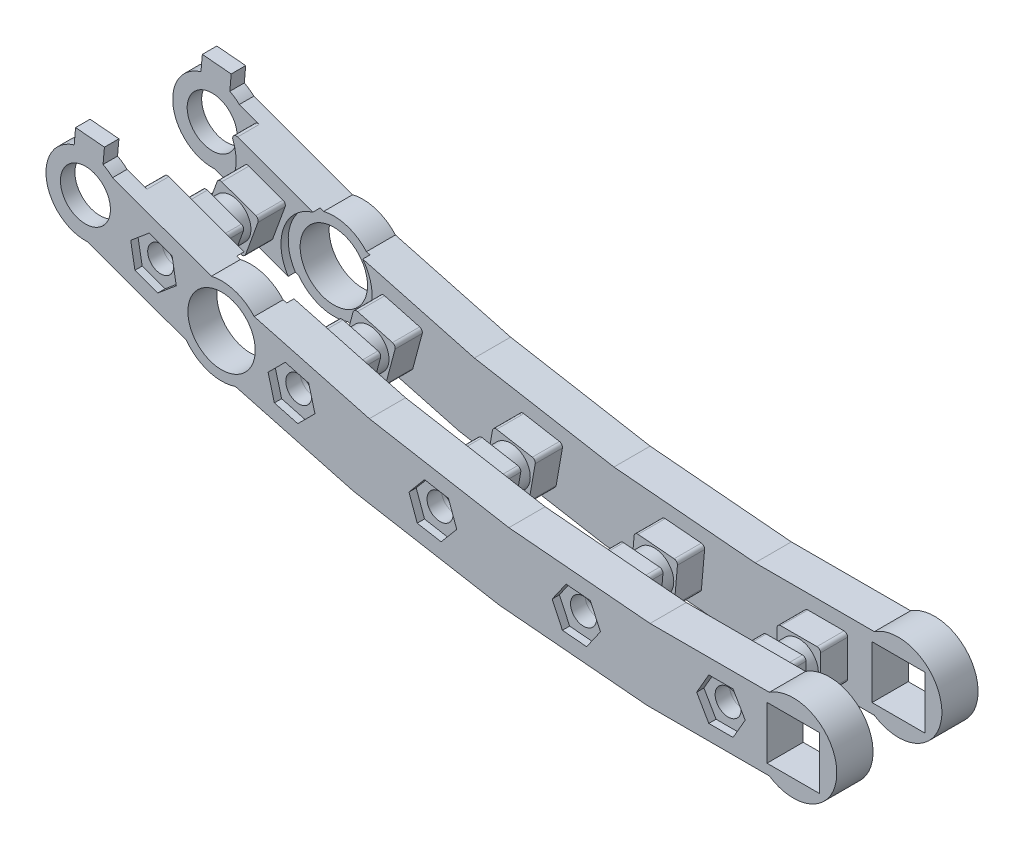
SolidWorks part; units mm, degrees
material "ABS"
ref_plane "正面" through (0, 0, 0) normal (0, 0, 1) x (1, 0, 0)
ref_plane "平面" through (0, 0, 0) normal (0, 1, 0) x (1, 0, 0)
ref_plane "右側面" through (0, 0, 0) normal (1, 0, 0) x (0, 0, -1)
sketch "ｽｹｯﾁ1" plane through (0, 0, 0) normal (0, 0, 1) x (1, 0, 0)
  line L0 (0, 0) -> (-20, 0) construction
  line L1 (3.64, -3.64) -> (-3.64, -3.64)
  line L2 (3.64, -3.64) -> (3.64, 3.64)
  line L3 (3.64, 3.64) -> (-3.64, 3.64)
  line L4 (-3.64, -3.64) -> (-3.64, 3.64)
  line L5 (3.64, -3.64) -> (-3.64, 3.64) construction
  line L6 (3.64, 3.64) -> (-3.64, -3.64) construction
  line L7 (-20, 0) -> (-39.9239, 1.7431) construction
  line L8 (-39.9239, 1.7431) -> (-59.62, 5.2161) construction
  line L9 (-59.62, 5.2161) -> (-78.9386, 10.3925) construction
  line L10 (-78.9386, 10.3925) -> (-97.7324, 17.2329) construction
  line L11 (0, 5) -> (-19.7817, 5) construction
  line L18 (-19.7817, 5) -> (-39.2706, 6.7051) construction
  line L19 (-39.2706, 6.7051) -> (-58.5368, 10.1022) construction
  line L20 (-58.5368, 10.1022) -> (-77.4336, 15.1656) construction
  line L21 (-77.4336, 15.1656) -> (-96.0223, 21.9313) construction
  line L22 (0, -5) -> (-20.2183, -5) construction
  line L23 (-20.2183, -5) -> (-40.5771, -3.2188) construction
  line L24 (-40.5771, -3.2188) -> (-60.7033, 0.3299) construction
  line L25 (-60.7033, 0.3299) -> (-80.4435, 5.6193) construction
  line L26 (-80.4435, 5.6193) -> (-99.4425, 12.5344) construction
  line L27 (-93.9846, 21.1896) -> (-77.4336, 15.1656)
  line L28 (-77.4336, 15.1656) -> (-58.5368, 10.1022)
  line L29 (-58.5368, 10.1022) -> (-39.2706, 6.7051)
  line L30 (-39.2706, 6.7051) -> (-19.7817, 5)
  line L31 (-19.7817, 5) -> (-3.3166, 5)
  line L32 (-3.3166, -5) -> (-20.2183, -5)
  line L33 (-20.2183, -5) -> (-40.5771, -3.2188)
  line L34 (-40.5771, -3.2188) -> (-60.7033, 0.3299)
  line L35 (-60.7033, 0.3299) -> (-80.4435, 5.6193)
  line L36 (-80.4435, 5.6193) -> (-97.4048, 11.7927)
  circle A0 centre (-10, 0) radius 1.8
  circle A1 centre (-29.9619, 0.8716) radius 1.8
  circle A2 centre (-49.772, 3.4796) radius 1.8
  circle A3 centre (-69.2793, 7.8043) radius 1.8
  circle A4 centre (-88.3355, 13.8127) radius 1.8
  circle A5 centre (-97.7324, 17.2329) radius 3.45
  arc A6 (-3.3166, -5) -> (-3.3166, 5) centre (0, 0) ccw
  arc A7 (-93.9846, 21.1896) -> (-97.4048, 11.7927) centre (-97.7324, 17.2329) ccw
  point P0 (0, 0)
  dimension "D8" = 3.6
  dimension "D9" = 6.9
  dimension "D10" = 12
  dimension "D13" = 10.9
  dimension "D1" = 7.28
  dimension "D2" = 7.28
  dimension "D3" = 175
  dimension "D4" = 175
  dimension "D5" = 175
  dimension "D6" = 175
  dimension "D7" = 20
  dimension "D11" = 5
  dimension "D12" = 5
extrude "ﾎﾞｽ - 押し出し1" add sketch "ｽｹｯﾁ1" along normal blind 2
sketch "ｽｹｯﾁ2" plane through (0, 0, 0) normal (0, 0, -1) x (-1, 0, 0)
  line L0 (91.2317, 20.1877) -> (77.4336, 15.1656)
  line L1 (94.6519, 10.7908) -> (80.4435, 5.6193)
  line L2 (97.4048, 11.7927) -> (80.4435, 5.6193) construction
  line L3 (77.4336, 15.1656) -> (93.9846, 21.1896) construction
  line L4 (-3.64, -3.64) -> (3.64, -3.64)
  line L5 (3.64, -3.64) -> (3.64, 3.64)
  line L6 (3.64, 3.64) -> (-3.64, 3.64)
  line L7 (-3.64, 3.64) -> (-3.64, -3.64)
  line L8 (-3.64, -3.64) -> (3.64, -3.64)
  line L9 (3.64, -3.64) -> (3.64, 3.64)
  line L10 (3.64, 3.64) -> (-3.64, 3.64)
  line L11 (-3.64, 3.64) -> (-3.64, -3.64)
  line L18 (93.9846, 21.1896) -> (77.4336, 15.1656)
  line L19 (77.4336, 15.1656) -> (58.5368, 10.1022)
  line L20 (58.5368, 10.1022) -> (39.2706, 6.7051)
  line L21 (39.2706, 6.7051) -> (19.7817, 5)
  line L22 (19.7817, 5) -> (3.3166, 5)
  line L23 (3.3166, -5) -> (20.2183, -5)
  line L24 (20.2183, -5) -> (40.5771, -3.2188)
  line L25 (40.5771, -3.2188) -> (60.7033, 0.3299)
  line L26 (60.7033, 0.3299) -> (80.4435, 5.6193)
  line L27 (80.4435, 5.6193) -> (97.4048, 11.7927)
  line L29 (77.4336, 15.1656) -> (58.5368, 10.1022)
  line L30 (58.5368, 10.1022) -> (39.2706, 6.7051)
  line L31 (39.2706, 6.7051) -> (19.7817, 5)
  line L32 (19.7817, 5) -> (3.3166, 5)
  line L33 (3.3166, -5) -> (20.2183, -5)
  line L34 (20.2183, -5) -> (40.5771, -3.2188)
  line L35 (40.5771, -3.2188) -> (60.7033, 0.3299)
  line L36 (60.7033, 0.3299) -> (80.4435, 5.6193)
  arc A0 (91.8682, 19.5351) -> (94.72, 11.6997) centre (97.7324, 17.2329) ccw
  circle A1 centre (29.9619, 0.8716) radius 1.8
  circle A2 centre (29.9619, 0.8716) radius 1.8
  circle A3 centre (10, 0) radius 1.8
  circle A4 centre (10, 0) radius 1.8
  arc A5 (94.6519, 10.7908) -> (94.72, 11.6997) centre (94.4809, 11.2606) ccw
  circle A7 centre (88.3355, 13.8127) radius 1.8
  circle A8 centre (88.3355, 13.8127) radius 1.8
  circle A9 centre (69.2793, 7.8043) radius 1.8
  circle A10 centre (69.2793, 7.8043) radius 1.8
  circle A11 centre (49.772, 3.4796) radius 1.8
  circle A12 centre (49.772, 3.4796) radius 1.8
  arc A13 (91.2317, 20.1877) -> (91.8682, 19.5351) centre (91.4027, 19.7178) cw
  arc A14 (3.3166, 5) -> (3.3166, -5) centre (0, 0) ccw
  arc A15 (97.4048, 11.7927) -> (93.9846, 21.1896) centre (97.7324, 17.2329) ccw
  arc A16 (3.3166, 5) -> (3.3166, -5) centre (0, 0) ccw
  point P41 (95.8409, 11.2235)
  point P46 (92.4207, 20.6204)
  dimension "D4" = 12.6
  dimension "D9" = 0.5
  dimension "D1" = 0
  dimension "D2" = 0
  dimension "D3" = 0
  dimension "D5" = 0
  dimension "D6" = 0
  dimension "D7" = 0
  dimension "D8" = 0
extrude "ﾎﾞｽ - 押し出し2" add sketch "ｽｹｯﾁ2" along normal blind 3
ref_plane "平面1" through (0, 0, -17.5) normal (0, 0, 1) x (1, 0, 0)
ref_plane "平面2" through (0, 0, -7.75) normal (0, 0, 1) x (1, 0, 0)
sketch "ｽｹｯﾁ3" plane through (0, 0, 2) normal (0, 0, 1) x (1, 0, 0)
  line L0 (-97.7324, 17.2329) -> (-95.8684, 22.3542) construction
  line L1 (-77.4336, 15.1656) -> (-93.9846, 21.1896) construction
  line L2 (-97.7324, 17.2329) -> (-97.2574, 22.6621) construction
  line L3 (-95.1081, 24.281) -> (-95.4219, 20.6947)
  line L4 (-95.1081, 24.281) -> (-99.0929, 24.6296)
  line L5 (-95.4219, 20.6947) -> (-99.4067, 21.0433)
  line L6 (-99.0929, 24.6296) -> (-99.4067, 21.0433)
  line L7 (-95.1081, 24.281) -> (-99.4067, 21.0433) construction
  line L8 (-95.4219, 20.6947) -> (-99.0929, 24.6296) construction
  arc A0 (-93.9846, 21.1896) -> (-97.4048, 11.7927) centre (-97.7324, 17.2329) ccw construction
  dimension "D1" = 1.8
  dimension "D2" = 4
  dimension "D3" = 15
extrude "ﾎﾞｽ - 押し出し3" add sketch "ｽｹｯﾁ3" against normal up to surface (2 mm away) up to face at (-95.0071, 16.2409, 0)
sketch "ｽｹｯﾁ4" plane through (0, 0, -17.5) normal (0, 0, 1) x (1, 0, 0)
  line L4 (-3.64, -3.64) -> (3.64, -3.64)
  line L5 (-3.64, 3.64) -> (-3.64, -3.64)
  line L6 (3.64, 3.64) -> (-3.64, 3.64)
  line L7 (3.64, -3.64) -> (3.64, 3.64)
  line L8 (-3.64, -3.64) -> (3.64, -3.64)
  line L9 (-3.64, 3.64) -> (-3.64, -3.64)
  line L10 (3.64, 3.64) -> (-3.64, 3.64)
  line L11 (3.64, -3.64) -> (3.64, 3.64)
  line L18 (-77.4336, 15.1656) -> (-93.9846, 21.1896)
  line L19 (-58.5368, 10.1022) -> (-77.4336, 15.1656)
  line L20 (-39.2706, 6.7051) -> (-58.5368, 10.1022)
  line L21 (-19.7817, 5) -> (-39.2706, 6.7051)
  line L22 (-3.3166, 5) -> (-19.7817, 5)
  line L23 (-20.2183, -5) -> (-3.3166, -5)
  line L24 (-40.5771, -3.2188) -> (-20.2183, -5)
  line L25 (-60.7033, 0.3299) -> (-40.5771, -3.2188)
  line L26 (-80.4435, 5.6193) -> (-60.7033, 0.3299)
  line L27 (-97.4048, 11.7927) -> (-80.4435, 5.6193)
  line L28 (-77.4336, 15.1656) -> (-93.9846, 21.1896)
  line L29 (-58.5368, 10.1022) -> (-77.4336, 15.1656)
  line L30 (-39.2706, 6.7051) -> (-58.5368, 10.1022)
  line L31 (-19.7817, 5) -> (-39.2706, 6.7051)
  line L32 (-3.3166, 5) -> (-19.7817, 5)
  line L33 (-20.2183, -5) -> (-3.3166, -5)
  line L34 (-40.5771, -3.2188) -> (-20.2183, -5)
  line L35 (-60.7033, 0.3299) -> (-40.5771, -3.2188)
  line L36 (-80.4435, 5.6193) -> (-60.7033, 0.3299)
  line L37 (-97.4048, 11.7927) -> (-80.4435, 5.6193)
  circle A1 centre (-29.9619, 0.8716) radius 1.8
  circle A2 centre (-29.9619, 0.8716) radius 1.8
  circle A3 centre (-10, 0) radius 1.8
  circle A4 centre (-10, 0) radius 1.8
  circle A5 centre (-97.7324, 17.2329) radius 3.45
  circle A6 centre (-97.7324, 17.2329) radius 3.45
  circle A7 centre (-88.3355, 13.8127) radius 1.8
  circle A8 centre (-88.3355, 13.8127) radius 1.8
  circle A9 centre (-69.2793, 7.8043) radius 1.8
  circle A10 centre (-69.2793, 7.8043) radius 1.8
  circle A11 centre (-49.772, 3.4796) radius 1.8
  circle A12 centre (-49.772, 3.4796) radius 1.8
  arc A14 (-3.3166, -5) -> (-3.3166, 5) centre (0, 0) ccw
  arc A15 (-93.9846, 21.1896) -> (-97.4048, 11.7927) centre (-97.7324, 17.2329) ccw
  arc A16 (-3.3166, -5) -> (-3.3166, 5) centre (0, 0) ccw
  arc A17 (-93.9846, 21.1896) -> (-97.4048, 11.7927) centre (-97.7324, 17.2329) ccw
  dimension "D1" = 0
  dimension "D2" = 0
  dimension "D3" = 0
  dimension "D4" = 0
  dimension "D5" = 0
  dimension "D6" = 0
  dimension "D7" = 0
  dimension "D8" = 0
extrude "ﾎﾞｽ - 押し出し4" add sketch "ｽｹｯﾁ4" along normal blind 2 separate body
sketch "ｽｹｯﾁ5" plane through (0, 0, -15.5) normal (0, 0, 1) x (1, 0, 0)
  line L4 (-3.64, -3.64) -> (3.64, -3.64)
  line L5 (-3.64, 3.64) -> (-3.64, -3.64)
  line L6 (3.64, 3.64) -> (-3.64, 3.64)
  line L7 (3.64, -3.64) -> (3.64, 3.64)
  line L8 (-3.64, -3.64) -> (3.64, -3.64)
  line L9 (-3.64, 3.64) -> (-3.64, -3.64)
  line L10 (3.64, 3.64) -> (-3.64, 3.64)
  line L11 (3.64, -3.64) -> (3.64, 3.64)
  line L18 (-80.4435, 5.6193) -> (-60.7033, 0.3299)
  line L19 (-60.7033, 0.3299) -> (-40.5771, -3.2188)
  line L20 (-40.5771, -3.2188) -> (-20.2183, -5)
  line L21 (-20.2183, -5) -> (-3.3166, -5)
  line L22 (-3.3166, 5) -> (-19.7817, 5)
  line L23 (-19.7817, 5) -> (-39.2706, 6.7051)
  line L24 (-39.2706, 6.7051) -> (-58.5368, 10.1022)
  line L25 (-58.5368, 10.1022) -> (-77.4336, 15.1656)
  line L26 (-77.4336, 15.1656) -> (-91.2317, 20.1877)
  line L27 (-94.6519, 10.7908) -> (-80.4435, 5.6193)
  line L28 (-80.4435, 5.6193) -> (-60.7033, 0.3299)
  line L29 (-60.7033, 0.3299) -> (-40.5771, -3.2188)
  line L30 (-40.5771, -3.2188) -> (-20.2183, -5)
  line L31 (-20.2183, -5) -> (-3.3166, -5)
  line L32 (-3.3166, 5) -> (-19.7817, 5)
  line L33 (-19.7817, 5) -> (-39.2706, 6.7051)
  line L34 (-39.2706, 6.7051) -> (-58.5368, 10.1022)
  line L35 (-58.5368, 10.1022) -> (-77.4336, 15.1656)
  line L36 (-77.4336, 15.1656) -> (-91.2317, 20.1877)
  line L37 (-94.6519, 10.7908) -> (-80.4435, 5.6193)
  circle A1 centre (-10, 0) radius 1.8
  circle A2 centre (-10, 0) radius 1.8
  circle A3 centre (-29.9619, 0.8716) radius 1.8
  circle A4 centre (-29.9619, 0.8716) radius 1.8
  circle A5 centre (-49.772, 3.4796) radius 1.8
  circle A6 centre (-49.772, 3.4796) radius 1.8
  circle A7 centre (-69.2793, 7.8043) radius 1.8
  circle A8 centre (-69.2793, 7.8043) radius 1.8
  circle A9 centre (-88.3355, 13.8127) radius 1.8
  circle A10 centre (-88.3355, 13.8127) radius 1.8
  arc A12 (-3.3166, -5) -> (-3.3166, 5) centre (0, 0) ccw
  arc A13 (-94.72, 11.6997) -> (-91.8682, 19.5351) centre (-97.7324, 17.2329) ccw
  arc A14 (-3.3166, -5) -> (-3.3166, 5) centre (0, 0) ccw
  arc A15 (-94.72, 11.6997) -> (-91.8682, 19.5351) centre (-97.7324, 17.2329) ccw
  arc A18 (-94.72, 11.6997) -> (-94.6519, 10.7908) centre (-94.4809, 11.2606) ccw
  arc A19 (-94.72, 11.6997) -> (-94.6519, 10.7908) centre (-94.4809, 11.2606) ccw
  arc A20 (-91.2317, 20.1877) -> (-91.8682, 19.5351) centre (-91.4027, 19.7178) ccw
  arc A21 (-91.2317, 20.1877) -> (-91.8682, 19.5351) centre (-91.4027, 19.7178) ccw
  dimension "D1" = 0
  dimension "D2" = 0
  dimension "D3" = 0
  dimension "D4" = 0
  dimension "D5" = 0
  dimension "D6" = 0
  dimension "D7" = 0
extrude "ﾎﾞｽ - 押し出し5" add sketch "ｽｹｯﾁ5" along normal blind 3
sketch "ｽｹｯﾁ6" plane through (0, 0, -17.5) normal (0, 0, -1) x (-1, 0, 0)
  line L4 (95.1081, 24.281) -> (95.4219, 20.6947)
  line L5 (95.4219, 20.6947) -> (99.4067, 21.0433)
  line L6 (99.4067, 21.0433) -> (99.0929, 24.6296)
  line L7 (99.0929, 24.6296) -> (95.1081, 24.281)
  line L8 (95.1081, 24.281) -> (95.4219, 20.6947)
  line L9 (95.4219, 20.6947) -> (99.4067, 21.0433)
  line L10 (99.4067, 21.0433) -> (99.0929, 24.6296)
  line L11 (99.0929, 24.6296) -> (95.1081, 24.281)
  dimension "D1" = 0
extrude "ﾎﾞｽ - 押し出し6" add sketch "ｽｹｯﾁ6" against normal up to surface (2 mm away) up to face at (-95.0071, 16.2409, -15.5)
sketch "ｽｹｯﾁ7" plane through (0, 0, -3) normal (0, 0, -1) x (-1, 0, 0)
  line L0 (27.1439, -2.4868) -> (26.6036, 3.6896)
  line L1 (6.9, -3.1) -> (13.1, -3.1)
  line L2 (6.9, -3.1) -> (6.9, 3.1)
  line L3 (6.9, 3.1) -> (13.1, 3.1)
  line L4 (13.1, -3.1) -> (13.1, 3.1)
  line L5 (6.9, -3.1) -> (13.1, 3.1) construction
  line L6 (6.9, 3.1) -> (13.1, -3.1) construction
  line L7 (27.1439, -2.4868) -> (33.3203, -1.9465)
  line L8 (26.6036, 3.6896) -> (32.78, 4.2299)
  line L9 (33.3203, -1.9465) -> (32.78, 4.2299)
  line L10 (27.1439, -2.4868) -> (32.78, 4.2299) construction
  line L11 (26.6036, 3.6896) -> (33.3203, -1.9465) construction
  line L12 (47.2574, -0.1116) -> (46.1808, 5.9942)
  line L13 (47.2574, -0.1116) -> (53.3632, 0.965)
  line L14 (46.1808, 5.9942) -> (52.2866, 7.0708)
  line L15 (53.3632, 0.965) -> (52.2866, 7.0708)
  line L16 (47.2574, -0.1116) -> (52.2866, 7.0708) construction
  line L17 (46.1808, 5.9942) -> (53.3632, 0.965) construction
  line L18 (67.0873, 4.0076) -> (65.4826, 9.9963)
  line L19 (67.0873, 4.0076) -> (73.076, 5.6122)
  line L20 (65.4826, 9.9963) -> (71.4713, 11.601)
  line L21 (73.076, 5.6122) -> (71.4713, 11.601)
  line L22 (67.0873, 4.0076) -> (71.4713, 11.601) construction
  line L23 (65.4826, 9.9963) -> (73.076, 5.6122) construction
  line L24 (90.1883, 17.786) -> (84.3622, 15.6654)
  line L25 (90.1883, 17.786) -> (92.3088, 11.9599)
  line L26 (84.3622, 15.6654) -> (86.4827, 9.8394)
  line L27 (92.3088, 11.9599) -> (86.4827, 9.8394)
  line L28 (90.1883, 17.786) -> (86.4827, 9.8394) construction
  line L29 (84.3622, 15.6654) -> (92.3088, 11.9599) construction
  line L30 (19.7817, 5) -> (39.2706, 6.7051) construction
  line L31 (39.2706, 6.7051) -> (58.5368, 10.1022) construction
  line L32 (58.5368, 10.1022) -> (77.4336, 15.1656) construction
  line L33 (77.4336, 15.1656) -> (93.9846, 21.1896) construction
  circle A0 centre (29.9619, 0.8716) radius 1.8 construction
  circle A1 centre (49.772, 3.4796) radius 1.8 construction
  circle A2 centre (69.2793, 7.8043) radius 1.8 construction
  circle A3 centre (88.3355, 13.8127) radius 1.8 construction
  point P0 (10, 0)
  point P7 (29.9619, 0.8716)
  point P8 (49.772, 3.4796)
  point P9 (69.2793, 7.8043)
  point P14 (88.3355, 13.8127)
  dimension "D1" = 6.2
  dimension "D2" = 6.2
extrude "ｶｯﾄ - 押し出し1" cut sketch "ｽｹｯﾁ7" against normal blind 2
sketch "ｽｹｯﾁ8" plane through (0, 0, -12.5) normal (0, 0, 1) x (1, 0, 0)
  line L0 (-13, -3) -> (-7, -3)
  line L1 (-7, -3) -> (-7, 3)
  line L2 (-7, 3) -> (-13, 3)
  line L3 (-13, 3) -> (-13, -3)
  line L4 (-13.1, -3.1) -> (-6.9, -3.1)
  line L5 (-13.1, 3.1) -> (-13.1, -3.1)
  line L6 (-6.9, 3.1) -> (-13.1, 3.1)
  line L7 (-6.9, -3.1) -> (-6.9, 3.1)
  line L8 (-13.1, -3.1) -> (-6.9, -3.1) construction
  line L9 (-13.1, 3.1) -> (-13.1, -3.1) construction
  line L10 (-6.9, 3.1) -> (-13.1, 3.1) construction
  line L11 (-6.9, -3.1) -> (-6.9, 3.1) construction
  line L12 (-27.1439, -2.4868) -> (-26.6036, 3.6896)
  line L13 (-26.6036, 3.6896) -> (-32.78, 4.2299)
  line L14 (-32.78, 4.2299) -> (-33.3203, -1.9465)
  line L15 (-33.3203, -1.9465) -> (-27.1439, -2.4868)
  line L16 (-27.1439, -2.4868) -> (-26.6036, 3.6896) construction
  line L17 (-26.6036, 3.6896) -> (-32.78, 4.2299) construction
  line L18 (-32.78, 4.2299) -> (-33.3203, -1.9465) construction
  line L19 (-33.3203, -1.9465) -> (-27.1439, -2.4868) construction
  line L20 (-84.3622, 15.6654) -> (-90.1883, 17.786)
  line L21 (-86.4827, 9.8394) -> (-84.3622, 15.6654)
  line L22 (-92.3088, 11.9599) -> (-86.4827, 9.8394)
  line L23 (-90.1883, 17.786) -> (-92.3088, 11.9599)
  line L24 (-84.3622, 15.6654) -> (-90.1883, 17.786) construction
  line L25 (-86.4827, 9.8394) -> (-84.3622, 15.6654) construction
  line L26 (-92.3088, 11.9599) -> (-86.4827, 9.8394) construction
  line L27 (-90.1883, 17.786) -> (-92.3088, 11.9599) construction
  line L28 (-67.0873, 4.0076) -> (-65.4826, 9.9963)
  line L29 (-65.4826, 9.9963) -> (-71.4713, 11.601)
  line L30 (-71.4713, 11.601) -> (-73.076, 5.6122)
  line L31 (-73.076, 5.6122) -> (-67.0873, 4.0076)
  line L32 (-67.0873, 4.0076) -> (-65.4826, 9.9963) construction
  line L33 (-65.4826, 9.9963) -> (-71.4713, 11.601) construction
  line L34 (-71.4713, 11.601) -> (-73.076, 5.6122) construction
  line L35 (-73.076, 5.6122) -> (-67.0873, 4.0076) construction
  line L36 (-47.2574, -0.1116) -> (-46.1808, 5.9942)
  line L37 (-53.3632, 0.965) -> (-47.2574, -0.1116)
  line L38 (-52.2866, 7.0708) -> (-53.3632, 0.965)
  line L39 (-46.1808, 5.9942) -> (-52.2866, 7.0708)
  line L40 (-47.2574, -0.1116) -> (-46.1808, 5.9942) construction
  line L41 (-53.3632, 0.965) -> (-47.2574, -0.1116) construction
  line L42 (-52.2866, 7.0708) -> (-53.3632, 0.965) construction
  line L43 (-46.1808, 5.9942) -> (-52.2866, 7.0708) construction
  line L44 (-27.2348, -2.3785) -> (-26.7119, 3.5987)
  line L45 (-26.7119, 3.5987) -> (-32.6891, 4.1216)
  line L46 (-32.6891, 4.1216) -> (-33.212, -1.8556)
  line L47 (-33.212, -1.8556) -> (-27.2348, -2.3785)
  line L48 (-84.4904, 15.6057) -> (-90.1285, 17.6578)
  line L49 (-90.1285, 17.6578) -> (-92.1806, 12.0196)
  line L50 (-92.1806, 12.0196) -> (-86.5425, 9.9675)
  line L51 (-86.5425, 9.9675) -> (-84.4904, 15.6057)
  line L52 (-67.158, 4.13) -> (-65.6051, 9.9256)
  line L53 (-65.6051, 9.9256) -> (-71.4006, 11.4785)
  line L54 (-71.4006, 11.4785) -> (-72.9535, 5.6829)
  line L55 (-72.9535, 5.6829) -> (-67.158, 4.13)
  line L56 (-47.3385, 0.0042) -> (-46.2966, 5.9131)
  line L57 (-46.2966, 5.9131) -> (-52.2055, 6.955)
  line L58 (-52.2055, 6.955) -> (-53.2473, 1.0461)
  line L59 (-53.2473, 1.0461) -> (-47.3385, 0.0042)
  circle A0 centre (-88.3355, 13.8127) radius 1.8 construction
  circle A1 centre (-69.2793, 7.8043) radius 1.8 construction
  circle A2 centre (-49.772, 3.4796) radius 1.8 construction
  circle A3 centre (-29.9619, 0.8716) radius 1.8 construction
  circle A4 centre (-10, 0) radius 1.8 construction
  circle A5 centre (-88.3355, 13.8127) radius 1.8
  circle A6 centre (-69.2793, 7.8043) radius 1.8
  circle A7 centre (-49.772, 3.4796) radius 1.8
  circle A8 centre (-29.9619, 0.8716) radius 1.8
  circle A9 centre (-10, 0) radius 1.8
  dimension "D1" = 0
  dimension "D2" = 0
  dimension "D3" = 0
  dimension "D4" = 0
  dimension "D5" = 0
  dimension "D6" = 0.1
extrude "ﾎﾞｽ - 押し出し7" add sketch "ｽｹｯﾁ8" along normal up to surface (11.5 mm away) up to face at (-8.2, 0, -1)
sketch "ｽｹｯﾁ9" plane through (0, 0, -7.75) normal (0, 0, 1) x (1, 0, 0)
  line L4 (-84.4904, 15.6057) -> (-90.1285, 17.6578)
  line L5 (-90.1285, 17.6578) -> (-92.1806, 12.0196)
  line L6 (-92.1806, 12.0196) -> (-86.5425, 9.9675)
  line L7 (-86.5425, 9.9675) -> (-84.4904, 15.6057)
  line L8 (-84.4904, 15.6057) -> (-90.1285, 17.6578)
  line L9 (-90.1285, 17.6578) -> (-92.1806, 12.0196)
  line L10 (-92.1806, 12.0196) -> (-86.5425, 9.9675)
  line L11 (-86.5425, 9.9675) -> (-84.4904, 15.6057)
  line L12 (-27.2348, -2.3785) -> (-26.7119, 3.5987)
  line L13 (-26.7119, 3.5987) -> (-32.6891, 4.1216)
  line L14 (-32.6891, 4.1216) -> (-33.212, -1.8556)
  line L15 (-33.212, -1.8556) -> (-27.2348, -2.3785)
  line L16 (-27.2348, -2.3785) -> (-26.7119, 3.5987)
  line L17 (-26.7119, 3.5987) -> (-32.6891, 4.1216)
  line L18 (-32.6891, 4.1216) -> (-33.212, -1.8556)
  line L19 (-33.212, -1.8556) -> (-27.2348, -2.3785)
  line L20 (-13, -3) -> (-7, -3)
  line L21 (-7, -3) -> (-7, 3)
  line L22 (-7, 3) -> (-13, 3)
  line L23 (-13, 3) -> (-13, -3)
  line L24 (-13, -3) -> (-7, -3)
  line L25 (-7, -3) -> (-7, 3)
  line L26 (-7, 3) -> (-13, 3)
  line L27 (-13, 3) -> (-13, -3)
  line L28 (-47.3385, 0.0042) -> (-46.2966, 5.9131)
  line L29 (-46.2966, 5.9131) -> (-52.2055, 6.955)
  line L30 (-52.2055, 6.955) -> (-53.2473, 1.0461)
  line L31 (-53.2473, 1.0461) -> (-47.3385, 0.0042)
  line L32 (-47.3385, 0.0042) -> (-46.2966, 5.9131)
  line L33 (-46.2966, 5.9131) -> (-52.2055, 6.955)
  line L34 (-52.2055, 6.955) -> (-53.2473, 1.0461)
  line L35 (-53.2473, 1.0461) -> (-47.3385, 0.0042)
  line L36 (-67.158, 4.13) -> (-65.6051, 9.9256)
  line L37 (-65.6051, 9.9256) -> (-71.4006, 11.4785)
  line L38 (-71.4006, 11.4785) -> (-72.9535, 5.6829)
  line L39 (-72.9535, 5.6829) -> (-67.158, 4.13)
  line L40 (-67.158, 4.13) -> (-65.6051, 9.9256)
  line L41 (-65.6051, 9.9256) -> (-71.4006, 11.4785)
  line L42 (-71.4006, 11.4785) -> (-72.9535, 5.6829)
  line L43 (-72.9535, 5.6829) -> (-67.158, 4.13)
  circle A0 centre (-88.3355, 13.8127) radius 2.7
  circle A1 centre (-69.2793, 7.8043) radius 2.7
  circle A3 centre (-49.772, 3.4796) radius 2.7
  circle A5 centre (-29.9619, 0.8716) radius 2.7
  circle A7 centre (-10, 0) radius 2.7
  dimension "D6" = 5.4
  dimension "D1" = 0
  dimension "D2" = 0
  dimension "D3" = 0
  dimension "D4" = 0
  dimension "D5" = 0
extrude "ｶｯﾄ - 押し出し2" cut sketch "ｽｹｯﾁ9" against normal blind 1 and the other way blind 1
sketch "ｽｹｯﾁ10" plane through (0, 0, 2) normal (0, 0, 1) x (1, 0, 0)
  line L1 (-11.6743, 2.9) -> (-13.3486, 0)
  line L2 (-13.3486, 0) -> (-11.6743, -2.9)
  line L3 (-11.6743, -2.9) -> (-8.3257, -2.9)
  line L4 (-8.3257, -2.9) -> (-6.6514, 0)
  line L5 (-6.6514, 0) -> (-8.3257, 2.9)
  line L6 (-8.3257, 2.9) -> (-11.6743, 2.9)
  line L7 (-31.8826, -1.8715) -> (-28.5468, -2.1633)
  line L8 (-28.5468, -2.1633) -> (-26.6261, 0.5797)
  line L9 (-26.6261, 0.5797) -> (-28.0413, 3.6146)
  line L10 (-28.0413, 3.6146) -> (-31.3771, 3.9064)
  line L11 (-31.3771, 3.9064) -> (-33.2978, 1.1634)
  line L12 (-33.2978, 1.1634) -> (-31.8826, -1.8715)
  line L13 (-51.9244, 0.9144) -> (-48.6267, 0.3329)
  line L14 (-48.6267, 0.3329) -> (-46.4742, 2.8981)
  line L15 (-46.4742, 2.8981) -> (-47.6195, 6.0448)
  line L16 (-47.6195, 6.0448) -> (-50.9173, 6.6263)
  line L17 (-50.9173, 6.6263) -> (-53.0697, 4.0611)
  line L18 (-53.0697, 4.0611) -> (-51.9244, 0.9144)
  line L19 (-71.6471, 5.4364) -> (-68.4126, 4.5697)
  line L20 (-68.4126, 4.5697) -> (-66.0448, 6.9376)
  line L21 (-66.0448, 6.9376) -> (-66.9115, 10.1721)
  line L22 (-66.9115, 10.1721) -> (-70.146, 11.0388)
  line L23 (-70.146, 11.0388) -> (-72.5138, 8.671)
  line L24 (-72.5138, 8.671) -> (-71.6471, 5.4364)
  line L25 (-90.9007, 11.6602) -> (-87.754, 10.5149)
  line L26 (-87.754, 10.5149) -> (-85.1888, 12.6674)
  line L27 (-85.1888, 12.6674) -> (-85.7703, 15.9651)
  line L28 (-85.7703, 15.9651) -> (-88.917, 17.1104)
  line L29 (-88.917, 17.1104) -> (-91.4822, 14.958)
  line L30 (-91.4822, 14.958) -> (-90.9007, 11.6602)
  line L31 (-19.7817, 5) -> (-39.2706, 6.7051) construction
  line L32 (-39.2706, 6.7051) -> (-58.5368, 10.1022) construction
  line L33 (-58.5368, 10.1022) -> (-77.4336, 15.1656) construction
  line L34 (-77.4336, 15.1656) -> (-93.9846, 21.1896) construction
  circle A0 centre (-10, 0) radius 2.9 construction
  circle A1 centre (-29.9619, 0.8716) radius 2.9 construction
  circle A2 centre (-49.772, 3.4796) radius 2.9 construction
  circle A3 centre (-69.2793, 7.8043) radius 2.9 construction
  circle A4 centre (-88.3355, 13.8127) radius 2.9 construction
  dimension "D1" = 5.8
extrude "ｶｯﾄ - 押し出し3" cut sketch "ｽｹｯﾁ10" against normal blind 1
sketch "ｽｹｯﾁ11" plane through (0, 0, -17.5) normal (0, 0, -1) x (-1, 0, 0)
  circle A0 centre (10, 0) radius 3.25
  circle A1 centre (29.9619, 0.8716) radius 3.25
  circle A2 centre (49.772, 3.4796) radius 3.25
  circle A3 centre (69.2793, 7.8043) radius 3.25
  circle A4 centre (88.3355, 13.8127) radius 3.25
  dimension "D1" = 6.5
extrude "ｶｯﾄ - 押し出し4" cut sketch "ｽｹｯﾁ11" against normal blind 1.5
sketch "ｽｹｯﾁ12" plane through (0, 0, 2) normal (0, 0, 1) x (1, 0, 0)
  circle A0 centre (-78.9386, 10.3925) radius 4.65
  dimension "D1" = 9.3
extrude "ｶｯﾄ - 押し出し5" cut sketch "ｽｹｯﾁ12" against normal through all
sketch "ｽｹｯﾁ13" plane through (0, 0, -3) normal (0, 0, -1) x (-1, 0, 0)
  circle A0 centre (78.9386, 10.3925) radius 6.3
  dimension "D1" = 12.6
extrude "ｶｯﾄ - 押し出し6" cut sketch "ｽｹｯﾁ13" against normal blind 1
sketch "ｽｹｯﾁ14" plane through (0, 0, -12.5) normal (0, 0, 1) x (1, 0, 0)
  circle A1 centre (-78.9386, 10.3925) radius 6.3
  circle A2 centre (-78.9386, 10.3925) radius 6.3
  dimension "D1" = 0
extrude "ｶｯﾄ - 押し出し7" cut sketch "ｽｹｯﾁ14" against normal blind 1
sketch "ｽｹｯﾁ15" plane through (0, 0, -2) normal (0, 0, -1) x (-1, 0, 0)
  line L0 (74.4409, 14.3637) -> (77.4336, 15.1656)
  line L1 (77.4336, 15.1656) -> (80.3451, 16.2253)
  line L2 (77.4336, 15.1656) -> (93.9846, 21.1896) construction
  line L3 (58.5368, 10.1022) -> (77.4336, 15.1656) construction
  line L4 (77.029, 4.7044) -> (80.4435, 5.6193)
  line L5 (80.4435, 5.6193) -> (83.7653, 6.8283)
  line L6 (97.4048, 11.7927) -> (80.4435, 5.6193) construction
  line L7 (80.4435, 5.6193) -> (60.7033, 0.3299) construction
  arc A0 (77.029, 4.7044) -> (83.7653, 6.8283) centre (78.9386, 10.3925) ccw
  arc A1 (80.3451, 16.2253) -> (74.4409, 14.3637) centre (78.9386, 10.3925) ccw
  dimension "D1" = 12
extrude "ﾎﾞｽ - 押し出し8" add sketch "ｽｹｯﾁ15" against normal up to surface (4 mm away) up to face at (-74.2886, 10.3925, 2)
sketch "ｽｹｯﾁ16" plane through (0, 0, -13.5) normal (0, 0, 1) x (1, 0, 0)
  line L2 (-77.029, 4.7044) -> (-80.4435, 5.6193)
  line L3 (-80.4435, 5.6193) -> (-83.7653, 6.8283)
  line L4 (-77.029, 4.7044) -> (-80.4435, 5.6193)
  line L5 (-80.4435, 5.6193) -> (-83.7653, 6.8283)
  line L6 (-77.4336, 15.1656) -> (-74.4409, 14.3637)
  line L7 (-80.3451, 16.2253) -> (-77.4336, 15.1656)
  line L8 (-77.4336, 15.1656) -> (-74.4409, 14.3637)
  line L9 (-80.3451, 16.2253) -> (-77.4336, 15.1656)
  arc A1 (-83.7653, 6.8283) -> (-77.029, 4.7044) centre (-78.9386, 10.3925) ccw
  arc A2 (-83.7653, 6.8283) -> (-77.029, 4.7044) centre (-78.9386, 10.3925) ccw
  arc A3 (-74.4409, 14.3637) -> (-80.3451, 16.2253) centre (-78.9386, 10.3925) ccw
  arc A4 (-74.4409, 14.3637) -> (-80.3451, 16.2253) centre (-78.9386, 10.3925) ccw
  dimension "D1" = 0
  dimension "D2" = 0
extrude "ﾎﾞｽ - 押し出し9" add sketch "ｽｹｯﾁ16" against normal up to surface (4 mm away) up to face at (-74.2886, 10.3925, -17.5)
fillet "ﾌｨﾚｯﾄ1" radius 0.5 40 edges at (-7, -3, -10.625) (-7, -3, -3.875) (-13, -3, -10.625) (-13, -3, -3.875) (-7, 3, -10.625) (-7, 3, -3.875) (-13, 3, -10.625) (-13, 3, -3.875) (-33.212, -1.8556, -10.625) (-33.212, -1.8556, -3.875) (-27.2348, -2.3785, -3.875) (-27.2348, -2.3785, -10.625) (-26.7119, 3.5987, -10.625) (-26.7119, 3.5987, -3.875) (-32.6891, 4.1216, -10.625) (-32.6891, 4.1216, -3.875) (-53.2473, 1.0461, -10.625) (-53.2473, 1.0461, -3.875) (-47.3385, 0.0042, -10.625) (-47.3385, 0.0042, -3.875) (-46.2966, 5.9131, -3.875) (-46.2966, 5.9131, -10.625) (-52.2055, 6.955, -10.625) (-52.2055, 6.955, -3.875) (-67.158, 4.13, -3.875) (-67.158, 4.13, -10.625) (-65.6051, 9.9256, -10.625) (-65.6051, 9.9256, -3.875) (-72.9535, 5.6829, -10.625) (-71.4006, 11.4785, -10.625) (-72.9535, 5.6829, -3.875) (-71.4006, 11.4785, -3.875) (-92.1806, 12.0196, -10.625) (-92.1806, 12.0196, -3.875) (-86.5425, 9.9675, -3.875) (-86.5425, 9.9675, -10.625) (-84.4904, 15.6057, -10.625) (-90.1285, 17.6578, -10.625) (-84.4904, 15.6057, -3.875) (-90.1285, 17.6578, -3.875)
equation "\"D4@ｽｹｯﾁ1\"=\"D3@ｽｹｯﾁ1\""
equation "\"D5@ｽｹｯﾁ1\"=\"D3@ｽｹｯﾁ1\""
equation "\"D6@ｽｹｯﾁ1\"=\"D3@ｽｹｯﾁ1\""
